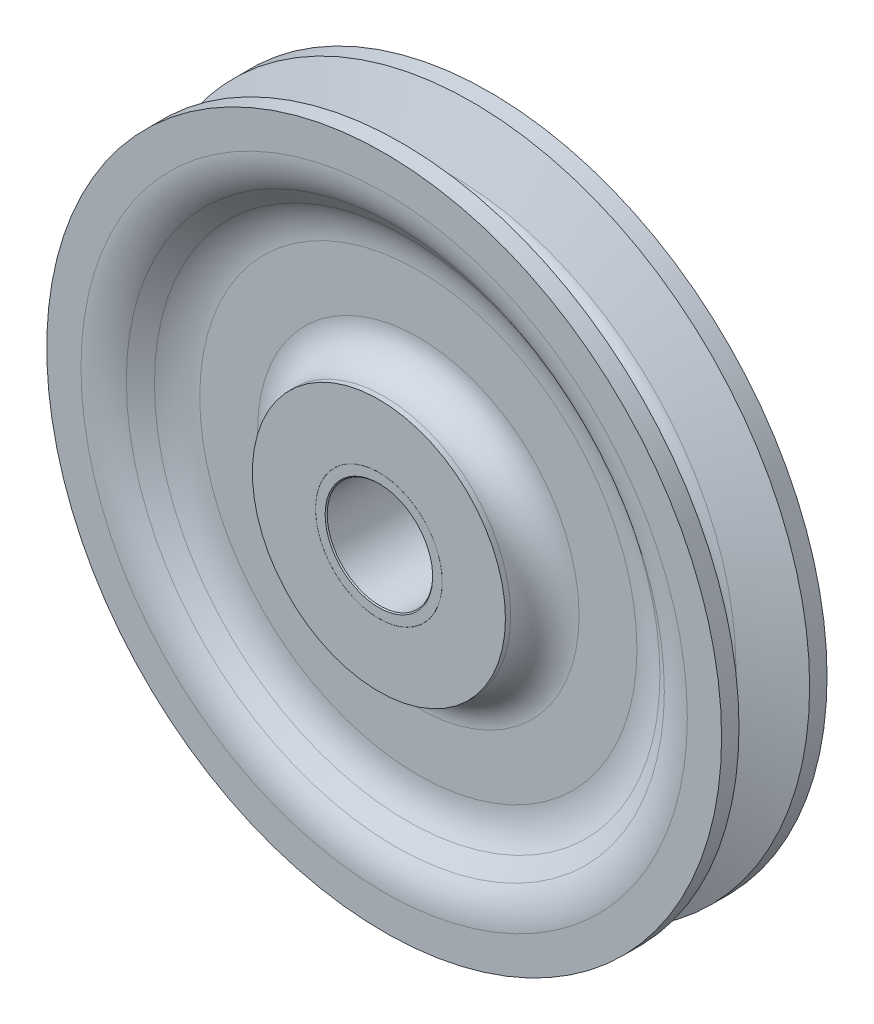
SolidWorks part; units mm, degrees
ref_plane "Front" through (0, 0, 0) normal (0, 0, 1) x (1, 0, 0)
ref_plane "Top" through (0, 0, 0) normal (0, 1, 0) x (1, 0, 0)
ref_plane "Right" through (0, 0, 0) normal (1, 0, 0) x (0, 0, -1)
sketch "Sketch1" plane through (0, 0, 0) normal (1, 0, 0) x (0, 0, -1)
  line L0 (10.6363, 101.6) -> (15.875, 101.6)
  line L1 (-10.6363, 101.6) -> (-15.875, 101.6)
  line L2 (-10.6363, 101.6) -> (-4.4415, 85.5936)
  line L3 (-15.875, 38.1) -> (-17.4625, 38.1)
  line L4 (17.4625, 15.875) -> (-17.4625, 15.875)
  line L5 (-17.4625, 38.1) -> (-17.4625, 19.05)
  line L6 (10.6363, 101.6) -> (4.4415, 85.5936)
  line L7 (-17.4625, 19.05) -> (17.4625, 19.05) construction
  line L8 (-17.4625, 0) -> (17.4625, 0) construction
  line L9 (-15.875, 38.1) -> (-15.875, 101.6)
  line L10 (15.875, 101.6) -> (15.875, 38.1)
  line L11 (15.875, 38.1) -> (17.4625, 38.1)
  line L12 (17.4625, 38.1) -> (17.4625, 19.05)
  line L13 (-17.4625, 19.05) -> (-17.4625, 15.875)
  line L14 (0, 82.55) -> (0, -82.55) construction
  line L16 (17.4625, 19.05) -> (17.4625, 15.875)
  line L17 (-15.875, 101.6) -> (-15.875, -101.6) construction
  arc A0 (-4.4415, 85.5936) -> (4.4415, 85.5936) centre (0, 87.3125) ccw
  circle A1 centre (0, 87.3125) radius 4.7625 construction
  circle A2 centre (0, 0) radius 15.875 construction
  circle A3 centre (0, 0) radius 19.05 construction
  circle A4 centre (0, 0) radius 38.1 construction
  circle A5 centre (0, -87.3125) radius 4.7625 construction
  point P28 (-15.875, 0)
  dimension "Rope Dia" = 9.525
  dimension "Shaft Dia" = 31.75
  dimension "bushing dia" = 38.1
  dimension "ring dia" = 76.2
  dimension "Wd" = 34.925
  dimension "D8" = 5.2387
  dimension "Groove Dia" = 165.1
  dimension "OD" = 203.2
  dimension "w Wd" = 31.75
  dimension "D1" = 3.175
revolve "Revolve1" add sketch "Sketch1" angle 360 about L8
sketch "Sketch2" plane through (0, 0, 0) normal (0, 0, 1) x (1, 0, 0)
  circle A1 centre (0, 0) radius 19.05
extrude "Cut-Extrude-Thin1" cut sketch "Sketch2" against normal through all and the other way through all thin
chamfer "Chamfer1" distance 0.3175 angle 45 2 edges at (15.875, 0, 17.4625) (15.875, 0, -17.4625)
sketch "Sketch3" plane through (0, 0, 0) normal (1, 0, 0) x (0, 0, -1)
  line L0 (-15.875, 38.1) -> (-5.588, 38.1)
  line L1 (-5.588, 38.1) -> (-5.588, 71.5115)
  line L2 (-15.875, 85.5936) -> (-15.875, 38.1)
  line L3 (-15.875, 38.1) -> (-15.875, 101.6) construction
  line L4 (-15.875, 85.5936) -> (-5.588, 71.5115)
  line L5 (-15.875, 85.5936) -> (-6.9615, 92.1049) construction
  line L6 (-5.588, 71.5115) -> (5.588, 71.5115) construction
  line L7 (0, 82.55) -> (0, -82.55) construction
  line L8 (-4.4415, 85.5936) -> (-10.6363, 101.6) construction
  line L9 (0, 82.55) -> (0, 71.5115) construction
  point P7 (0, 71.5115)
  dimension "neck thick a" = 11.176
revolve "Cut-Revolve1" cut sketch "Sketch3" angle 360
mirror "Mirror1" about plane through (0, 0, 0) normal (0, 0, 1) of "Cut-Revolve1"
fillet "Fillet2" radius 17.4392 4 edges at (-71.5115, 0, 5.588) (-85.5936, 0, 15.875) (-71.5115, 0, -5.588) (-85.5936, 0, -15.875)
fillet "Fillet3" radius 10.287 2 edges at (-38.1, 0, -5.588) (-38.1, 0, 5.588)
fillet "46" [suppressed] radius 6.0372
fillet "69" [suppressed] radius 10.16
equation "\"D8@Sketch1\" = \"Wd@Sketch1\" * .15"
equation "\"D1@Chamfer1\" = \"D1@Sketch1\" * .1"
equation "\"D1@Fillet2\" = \"D2@Sketch3\""
equation "\"D1@Fillet3\" = \"D3@Sketch3\""
